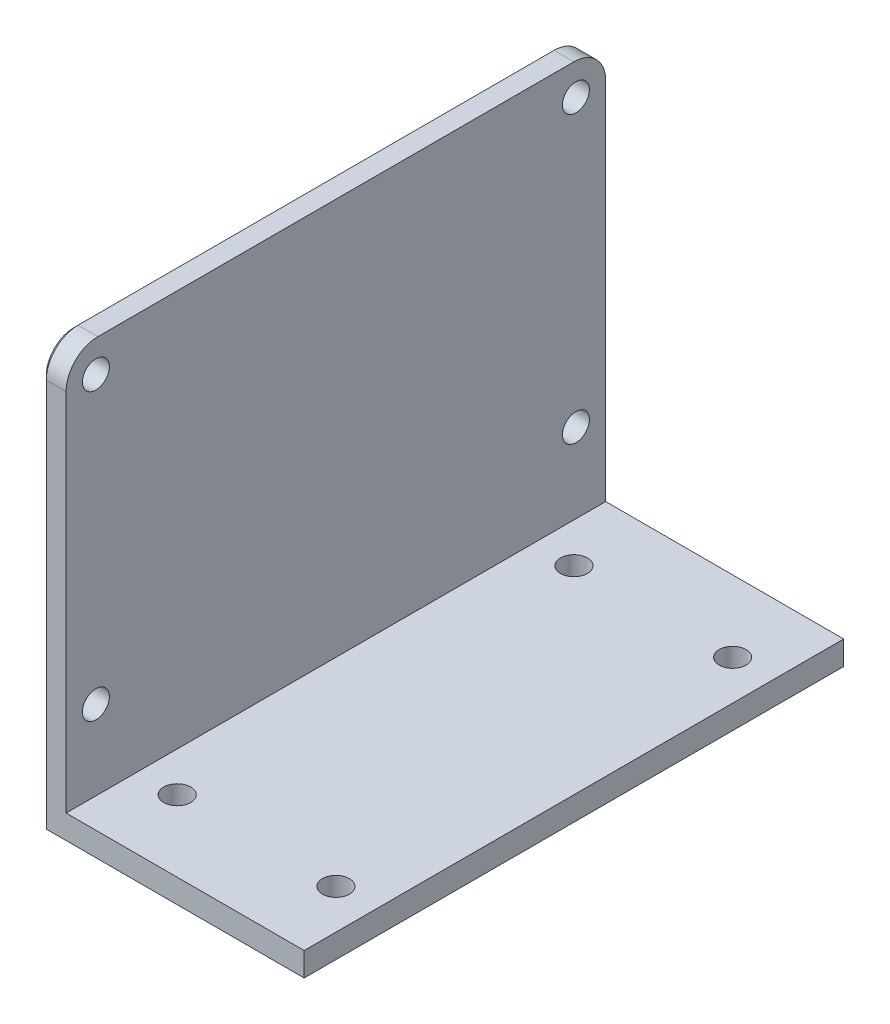
SolidWorks part; units mm, degrees
material "6061-T6 (SS)"
ref_plane "Front Plane" through (0, 0, 0) normal (0, 0, 1) x (1, 0, 0)
ref_plane "Top Plane" through (0, 0, 0) normal (0, 1, 0) x (1, 0, 0)
ref_plane "Right Plane" through (0, 0, 0) normal (1, 0, 0) x (0, 0, -1)
sketch "Sketch1" plane through (0, 0, 0) normal (0, 0, 1) x (1, 0, 0)
  line L0 (0, 0) -> (33, 0)
  line L1 (33, 0) -> (33, 3)
  line L2 (33, 3) -> (3, 3)
  line L3 (3, 3) -> (3, 53)
  line L4 (3, 53) -> (0, 53)
  line L5 (0, 53) -> (0, 0)
  dimension "D1" = 50
  dimension "D2" = 30
  dimension "D3" = 3
extrude "Boss-Extrude1" add sketch "Sketch1" along normal blind 68
sketch "Sketch2" plane through (3, 0, 0) normal (1, 0, 0) x (0, 0, -1)
  line L0 (-34, 31) -> (-34, 53) construction
  line L1 (-64.25, 49) -> (-3.75, 49) construction
  line L2 (-64.25, 49) -> (-64.25, 13) construction
  line L3 (-64.25, 13) -> (-3.75, 13) construction
  line L4 (-3.75, 49) -> (-3.75, 13) construction
  line L5 (-64.25, 49) -> (-3.75, 13) construction
  line L6 (-64.25, 13) -> (-3.75, 49) construction
  line L7 (-68, 53) -> (0, 53) construction
  point P0 (-34, 31)
  dimension "D1" = 60.5
  dimension "D2" = 36
  dimension "D3" = 4
hole_wizard "M3 Clearance Hole1" positions "Sketch4" profile "Sketch3" hole size "M3" standard "ANSI Metric"
sketch "Sketch4" plane through (3, 0, 0) normal (1, 0, 0) x (0, 0, -1)
  point P0 (-64.25, 49)
  point P3 (-3.75, 49)
  point P6 (-3.75, 13)
  point P9 (-64.25, 13)
sketch "Sketch3" plane through (3, 49, 64.25) normal (0, 1, 0) x (0, 0, -1)
  line L0 (0, 0) -> (0, 6.0215)
  line L1 (0, 6.0215) -> (1.7, 5)
  line L2 (1.7, 5) -> (1.7, 0)
  line L5 (1.7, 0) -> (0, 0)
  line L10 (0, 6.0215) -> (-1.7, 5) construction
  line L11 (0, -6.35) -> (0, 107.95) construction
  dimension "Hole Dia." = 3.4
  dimension "Hole Depth" = 5
  dimension "Drill Angle" = 118
sketch "Sketch5" plane through (0, 3, 0) normal (0, 1, 0) x (1, 0, 0)
  line L0 (18, 0) -> (18, -68) construction
  line L1 (33, 0) -> (3, 0) construction
  line L2 (33, -68) -> (3, -68) construction
  line L3 (3, -34) -> (33, -34) construction
  line L4 (3, -68) -> (3, 0) construction
  line L5 (33, -68) -> (33, 0) construction
  line L7 (8, -59) -> (28, -59) construction
  line L8 (8, -59) -> (8, -9) construction
  line L9 (8, -9) -> (28, -9) construction
  line L10 (28, -59) -> (28, -9) construction
  line L11 (8, -59) -> (28, -9) construction
  line L12 (8, -9) -> (28, -59) construction
  point P12 (18, -34)
  dimension "D1" = 20
  dimension "D2" = 50
hole_wizard "M3 Clearance Hole2" positions "Sketch7" profile "Sketch6" hole size "M3" standard "ANSI Metric"
sketch "Sketch7" plane through (0, 3, 0) normal (0, 1, 0) x (1, 0, 0)
  point P0 (28, -59)
  point P3 (8, -59)
  point P6 (8, -9)
  point P9 (28, -9)
sketch "Sketch6" plane through (28, 3, 59) normal (1, 0, 0) x (0, 0, 1)
  line L0 (0, 0) -> (0, 6.0215)
  line L1 (0, 6.0215) -> (1.7, 5)
  line L2 (1.7, 5) -> (1.7, 0)
  line L5 (1.7, 0) -> (0, 0)
  line L10 (0, 6.0215) -> (-1.7, 5) construction
  line L11 (0, -6.35) -> (0, 107.95) construction
  dimension "Hole Dia." = 3.4
  dimension "Hole Depth" = 5
  dimension "Drill Angle" = 118
fillet "Fillet1" radius 4 2 edges at (1.5, 53, 68) (1.5, 53, 0)
chamfer "Chamfer1" distance 0.5 angle 45 5 edges at (0, 24.5, 68) (0, 51.8284, 66.8284) (0, 53, 34) (0, 51.8284, 1.1716) (0, 24.5, 0)
